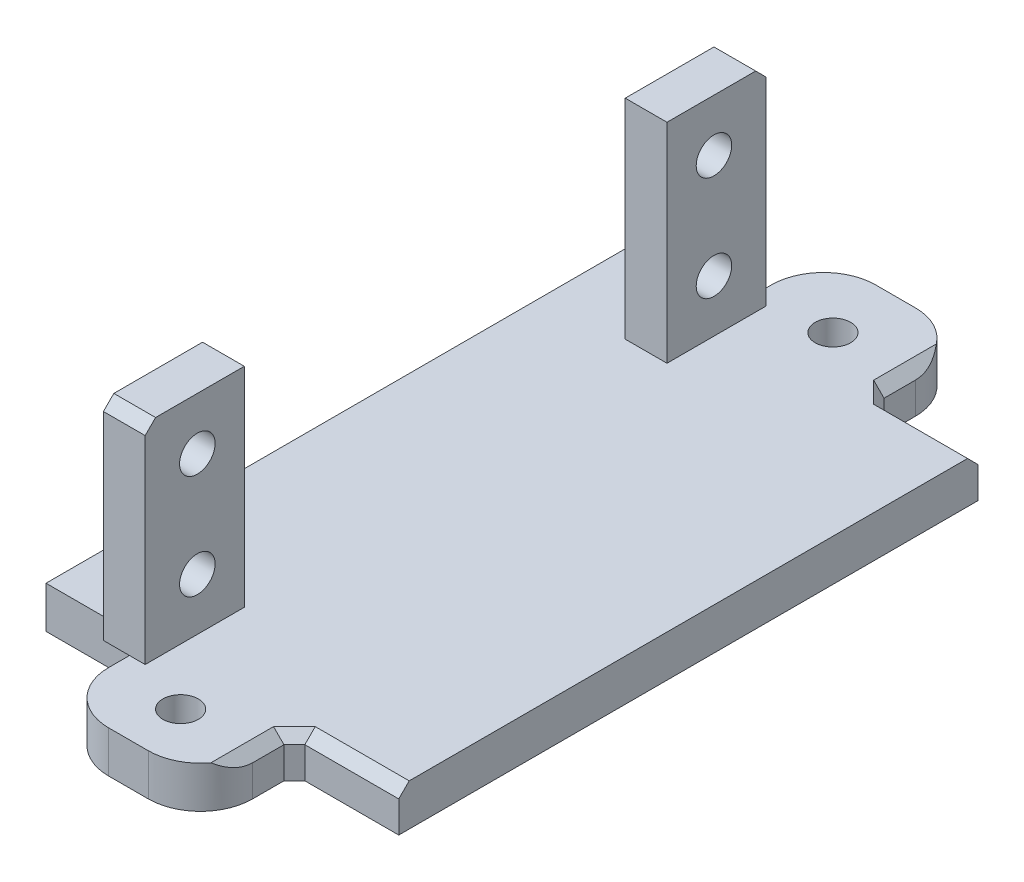
SolidWorks part; units mm, degrees
ref_plane "Front Plane" through (0, 0, 0) normal (0, 0, 1) x (1, 0, 0)
ref_plane "Top Plane" through (0, 0, 0) normal (0, 1, 0) x (1, 0, 0)
ref_plane "Right Plane" through (0, 0, 0) normal (1, 0, 0) x (0, 0, -1)
sketch "Sketch1" plane through (0, 0, 0) normal (0, 1, 0) x (1, 0, 0)
  line L1 (0, 0) -> (33.8, 0)
  line L2 (0, 0) -> (0, 55.5)
  line L3 (0, 55.5) -> (33.8, 55.5)
  line L4 (33.8, 0) -> (33.8, 55.5)
  dimension "D1" = 33.8
  dimension "D2" = 55.5
extrude "Boss-Extrude1" add sketch "Sketch1" along normal blind 4
sketch "Sketch3" plane through (0, 4, 0) normal (0, 1, 0) x (1, 0, 0)
  line L0 (0, 0) -> (33.8, 0) construction
  line L5 (7.5, 0) -> (11.5, 0)
  line L6 (7.5, 0) -> (7.5, 7.5)
  line L7 (7.5, 7.5) -> (11.5, 7.5)
  line L8 (11.5, 0) -> (11.5, 7.5)
  line L9 (33.8, 55.5) -> (0, 55.5) construction
  line L10 (7.5, 55.5) -> (11.5, 55.5)
  line L11 (7.5, 55.5) -> (7.5, 48)
  line L12 (7.5, 48) -> (11.5, 48)
  line L13 (11.5, 55.5) -> (11.5, 48)
  line L14 (0, 55.5) -> (0, 0) construction
  dimension "D1" = 4
  dimension "D2" = 7.5
  dimension "D3" = 7.5
  dimension "D4" = 4
  dimension "D5" = 7.5
  dimension "D6" = 7.5
extrude "Boss-Extrude2" add sketch "Sketch3" along normal blind 20
sketch "Sketch4" plane through (7.5, 0, 0) normal (-1, 0, 0) x (0, 0, 1)
  line L0 (0, 24) -> (0, 4) construction
  line L1 (-7.5, 24) -> (0, 24) construction
  line L2 (-48, 24) -> (-7.5, 24) construction
  line L3 (-27.75, 24) -> (-27.75, 8.8199) construction
  circle A0 centre (-3, 19) radius 1.7
  circle A1 centre (-3, 9) radius 1.7
  circle A2 centre (-52.5, 9) radius 1.7
  circle A3 centre (-52.5, 19) radius 1.7
  dimension "D2" = 3
  dimension "D3" = 5
  dimension "D4" = 10
  dimension "D5" = 3.4
  dimension "D6" = 3.4
  dimension "D1" = 3
extrude "Cut-Extrude1" cut sketch "Sketch4" against normal blind 20
sketch "Sketch5" plane through (0, 0, 0) normal (0, 0, 1) x (1, 0, 0)
  line L1 (11.5, 24) -> (7.5, 24)
  line L2 (11.5, 24) -> (11.5, 4)
  line L3 (11.5, 4) -> (7.5, 4)
  line L4 (7.5, 24) -> (7.5, 4)
extrude "Boss-Extrude3" add sketch "Sketch5" along normal blind 2
sketch "Sketch6" plane through (0, 0, -55.5) normal (0, 0, -1) x (-1, 0, 0)
  line L1 (-7.5, 24) -> (-11.5, 24)
  line L2 (-7.5, 24) -> (-7.5, 4)
  line L3 (-7.5, 4) -> (-11.5, 4)
  line L4 (-11.5, 24) -> (-11.5, 4)
extrude "Boss-Extrude4" add sketch "Sketch6" along normal blind 2
chamfer "Chamfer1" distance 2 angle 45 2 edges at (9.5, 4, 0) (9.5, 4, -55.5)
chamfer "Chamfer3" distance 1 angle 45 2 edges at (9.5, 24, 2) (9.5, 24, -57.5)
sketch "Sketch7" plane through (0, 0, 0) normal (0, -1, 0) x (1, 0, 0)
  line L0 (0, 0) -> (33.8, 0) construction
  line L1 (23.8, 0) -> (10, 0)
  line L2 (23.8, 0) -> (23.8, 9)
  line L3 (23.8, 9) -> (10, 9)
  line L4 (10, 0) -> (10, 9)
  line L5 (33.8, -55.5) -> (0, -55.5) construction
  line L6 (10, -55.5) -> (23.8, -55.5)
  line L7 (10, -55.5) -> (10, -64.5)
  line L8 (10, -64.5) -> (23.8, -64.5)
  line L9 (23.8, -55.5) -> (23.8, -64.5)
  line L10 (0, -55.5) -> (0, 0) construction
  line L11 (33.8, 0) -> (33.8, -55.5) construction
  dimension "D1" = 10
  dimension "D2" = 10
  dimension "D3" = 10
  dimension "D4" = 10
  dimension "D5" = 9
  dimension "D6" = 9
extrude "Boss-Extrude5" add sketch "Sketch7" against normal blind 4
chamfer "Chamfer4" distance 1 angle 45 8 edges at (23.8, 2, -55.5) (28.8, 4, -55.5) (10, 1, -55.5) (23.8, 2, 0) (28.8, 4, 0) (10, 1, 0) (23.8, 4, -60) (23.8, 4, 4.5)
fillet "Fillet1" radius 5 4 edges at (10, 2, -64.5) (23.8, 1.5, -64.5) (10, 2, 9) (23.8, 1.5, 9)
sketch "Sketch8" plane through (0, 4, 0) normal (0, 1, 0) x (1, 0, 0)
  line L0 (16.9, 64.5) -> (16.9, 54.5) construction
  line L3 (16.9, 1) -> (16.9, -9) construction
  line L6 (24.8, 1) -> (33.8, 1) construction
  line L7 (18.8, -9) -> (15, -9) construction
  line L10 (15, 64.5) -> (18.8, 64.5) construction
  line L11 (33.8, 54.5) -> (24.8, 54.5) construction
  circle A0 centre (16.9, 58.5) radius 1.7
  circle A1 centre (16.9, -4) radius 1.7
  dimension "D1" = 3.4
  dimension "D2" = 3.4
  dimension "D3" = 4
extrude "Cut-Extrude2" cut sketch "Sketch8" against normal blind 4
